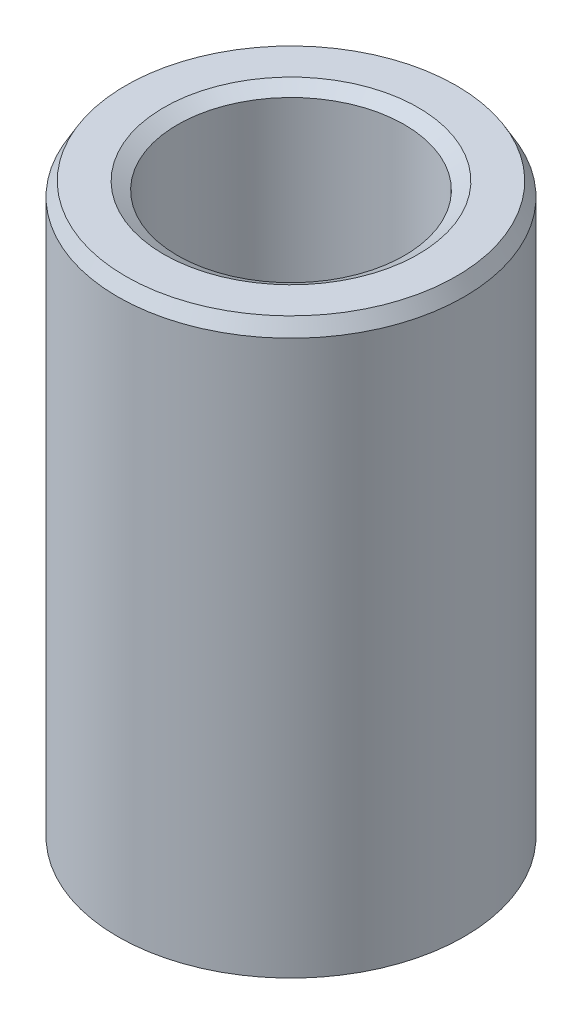
SolidWorks part; units mm, degrees
ref_plane "Front Plane" through (0, 0, 0) normal (0, 0, 1) x (1, 0, 0)
ref_plane "Top Plane" through (0, 0, 0) normal (0, 1, 0) x (1, 0, 0)
ref_plane "Right Plane" through (0, 0, 0) normal (1, 0, 0) x (0, 0, -1)
sketch "Sketch1" plane through (0, 0, 0) normal (0, 1, 0) x (1, 0, 0)
  circle A0 centre (0, 0) radius 50
  dimension "SLEEVE_OD" = 100
extrude "Boss-Extrude1" add sketch "Sketch1" along normal blind 166.2033
sketch "Sketch2" plane through (0, 0, 0) normal (0, 1, 0) x (1, 0, 0)
  circle A0 centre (0, 0) radius 32.742
  dimension "BORE_D" = 65.484
extrude "Cut-Extrude1" cut sketch "Sketch2" along normal through all
chamfer "Chamfer1" distance 3.9736 angle 30 4 edges at (0, 166.2033, 32.742) (0, 0, 32.742) (0, 0, 50) (0, 166.2033, 50) first distance on face at (0, 166.2033, 32.742) first distance on face at (0, 0, 32.742) first distance on face at (0, 166.2033, 50)
